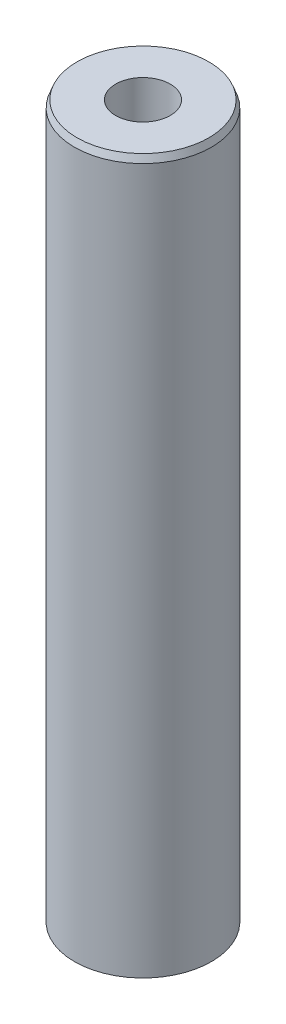
SolidWorks part; units mm, degrees
ref_plane "Front Plane" through (0, 0, 0) normal (0, 0, 1) x (1, 0, 0)
ref_plane "Top Plane" through (0, 0, 0) normal (0, 1, 0) x (1, 0, 0)
ref_plane "Right Plane" through (0, 0, 0) normal (1, 0, 0) x (0, 0, -1)
sketch "Sketch1" plane through (0, 0, 0) normal (0, 1, 0) x (1, 0, 0)
  circle A0 centre (0, 0) radius 57.5
  dimension "SHAFT_OD" = 115
extrude "Boss-Extrude1" add sketch "Sketch1" along normal blind 600
sketch "Sketch2" plane through (0, 0, 0) normal (0, 1, 0) x (1, 0, 0)
  circle A0 centre (0, 0) radius 22.9082
  dimension "BORE_D" = 45.8165
extrude "Cut-Extrude1" cut sketch "Sketch2" along normal through all
chamfer "Chamfer1" distance 5.7538 angle 20.832 2 edges at (0, 600, 57.5) (0, 0, 57.5) first distance on face at (0, 600, 57.5) first distance on face at (0, 0, 22.9082)
